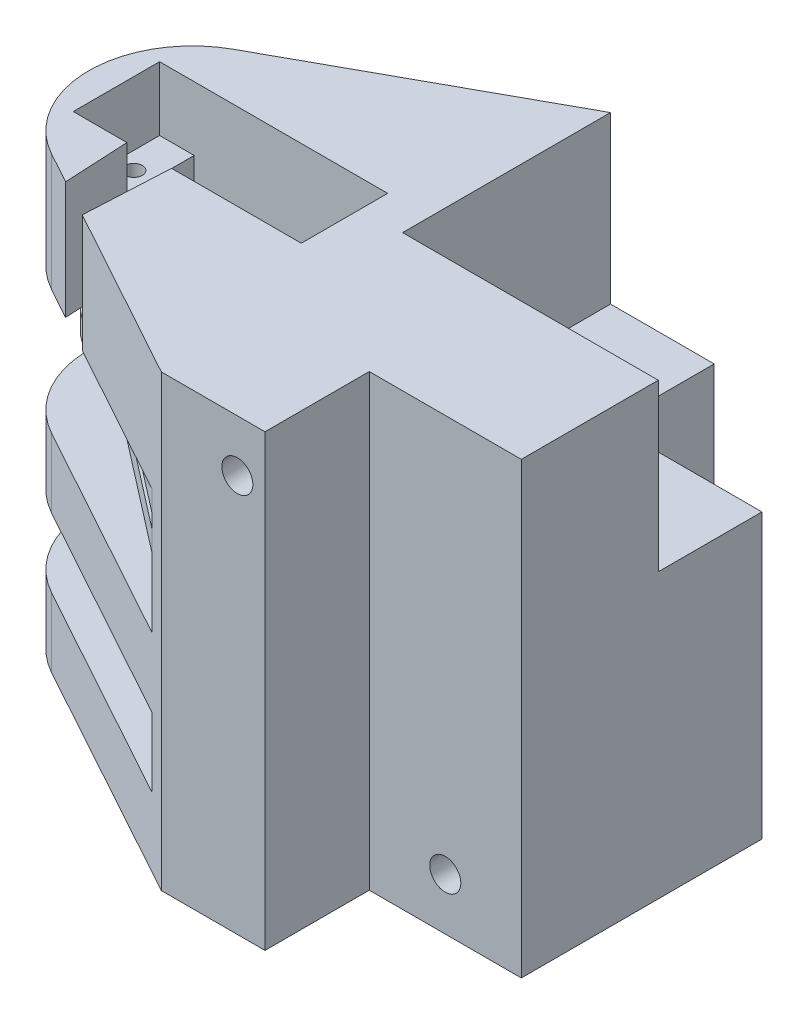
SolidWorks part; units mm, degrees
material "Copper"
ref_plane "Front Plane" through (0, 0, 0) normal (0, 0, 1) x (1, 0, 0)
ref_plane "Top Plane" through (0, 0, 0) normal (0, 1, 0) x (1, 0, 0)
ref_plane "Right Plane" through (0, 0, 0) normal (1, 0, 0) x (0, 0, -1)
sketch "Sketch1" plane through (0, 0, 0) normal (0, 0, 1) x (1, 0, 0)
  line L1 (0, 0) -> (80, 0)
  line L2 (0, 0) -> (0, 65)
  line L3 (0, 65) -> (80, 65)
  line L4 (80, 0) -> (80, 65)
  dimension "D1" = 65
  dimension "D2" = 80
extrude "Boss-Extrude1" add sketch "Sketch1" along normal blind 65
sketch "Sketch3" plane through (0, 0, 0) normal (0, -1, 0) x (1, 0, 0)
  line L0 (80, 32.5) -> (0, 32.5) construction
  line L1 (80, 65) -> (80, 0) construction
  line L2 (0, 65) -> (0, 0) construction
  line L3 (58, 49.91) -> (58, 32.5) construction
  line L4 (80, 65) -> (58, 65)
  line L5 (80, 65) -> (80, 49.91)
  line L6 (80, 49.91) -> (58, 49.91)
  line L7 (58, 65) -> (58, 49.91)
  line L8 (80, 0) -> (58, 0)
  line L9 (80, 0) -> (80, 15.09)
  line L10 (80, 15.09) -> (58, 15.09)
  line L11 (58, 0) -> (58, 15.09)
  line L12 (58, 32.5) -> (58, 15.09) construction
  dimension "D1" = 22
  dimension "D2" = 17.41
extrude "Cut-Extrude1" cut sketch "Sketch3" against normal blind 65.72
sketch "Sketch4" plane through (0, 0, 49.91) normal (0, 0, 1) x (1, 0, 0)
  line L0 (69, 0) -> (69, 65) construction
  line L1 (58, 0) -> (80, 0) construction
  line L2 (69, 7.5) -> (69, 0) construction
  line L3 (58, 65) -> (80, 65) construction
  line L4 (69, 65) -> (69, 57.5) construction
  line L5 (69, 57.5) -> (54, 57.5) construction
  circle A0 centre (69, 7.5) radius 2.2451
  circle A1 centre (69, 57.5) radius 2.2451
  circle A2 centre (54, 57.5) radius 2.245
  dimension "D1" = 4.4901
  dimension "D3" = 7.5
  dimension "D4" = 4.4901
  dimension "D5" = 4.49
  dimension "D2" = 7.5
  dimension "D6" = 15
extrude "Cut-Extrude2" cut sketch "Sketch4" against normal blind 55.72 and the other way blind 20 contours A2 | A0 region at (54, 57.5, 49.91)
sketch "Sketch5" plane through (0, 0, 0) normal (-1, 0, 0) x (0, 0, 1)
  line L0 (65, 65) -> (65, 0) construction
  line L1 (0, 0) -> (65, 0)
  line L2 (0, 0) -> (0, 10)
  line L3 (0, 10) -> (65, 10)
  line L4 (65, 0) -> (65, 10)
  line L6 (0, 10) -> (65, 10)
  line L7 (0, 10) -> (0, 20)
  line L8 (0, 20) -> (65, 20)
  line L9 (65, 10) -> (65, 20)
  line L10 (0, 20) -> (65, 20)
  line L11 (0, 20) -> (0, 30)
  line L12 (0, 30) -> (65, 30)
  line L13 (65, 20) -> (65, 30)
  line L14 (0, 30) -> (65, 30)
  line L15 (0, 30) -> (0, 40)
  line L16 (0, 40) -> (65, 40)
  line L17 (65, 30) -> (65, 40)
  line L18 (0, 40) -> (65, 40)
  line L19 (0, 40) -> (0, 43)
  line L20 (0, 43) -> (65, 43)
  line L21 (65, 40) -> (65, 43)
  line L22 (0, 43) -> (65, 43)
  line L23 (0, 43) -> (0, 45)
  line L24 (0, 45) -> (65, 45)
  line L25 (65, 43) -> (65, 45)
  line M3 (0, 65) -> (0, 0)
  line M5 (65, 0) -> (65, 65)
  dimension "D1" = 10
  dimension "D2" = 3
  dimension "D3" = 2
extrude "Cut-Extrude3" cut sketch "Sketch5" against normal blind 40 contours L16 L12 M3 M5 | L8 L3 M3 M5 | L23 L24 L25 L22 region at (0, 15, 32.5) region at (0, 35, 32.5)
sketch "Sketch6" plane through (0, 0, 0) normal (0, -1, 0) x (1, 0, 0)
  line L0 (0, 32.5) -> (48.8784, 32.5) construction
  line L1 (0, 65) -> (0, 0) construction
  line L2 (58, 0) -> (43, 0)
  line L3 (0, 0) -> (58, 0) construction
  line L4 (43, 0) -> (7.7767, 19.3538)
  line L5 (7.7767, 45.6462) -> (43, 65)
  line L6 (0, 65) -> (58, 65) construction
  line L7 (43, 0) -> (43, 65) construction
  line L8 (58, 15.09) -> (58, 0) construction
  line L9 (43, 14.0738) -> (58, 14.0738) construction
  line L10 (43, 0) -> (0, 0)
  line L11 (0, 0) -> (0, 32.5)
  line L12 (0, 32.5) -> (0, 65)
  line L13 (0, 65) -> (43, 65)
  circle A0 centre (15, 32.5) radius 15
  line M6 (58, 65) -> (0, 65)
  line M7 (0, 65) -> (0, 0)
  line M8 (0, 0) -> (58, 0)
  dimension "D1" = 15
  dimension "D2" = 30
extrude "Cut-Extrude4" cut sketch "Sketch6" against normal blind 65 contours A0 L4 M7 M8 | A0 L5 M6 M7 region at (14.0187, 0, 8.2899) region at (14.0187, 0, 56.7101)
sketch "Sketch10" plane through (0, 0, 0) normal (0, -1, 0) x (1, 0, 0)
  line L0 (0, 32.5) -> (15, 32.5) construction
  arc A0 (7.7767, 45.6462) -> (7.7767, 19.3538) centre (15, 32.5) ccw construction
  circle A1 centre (15, 32.5) radius 1
  dimension "D1" = 15
  dimension "D2" = 2
extrude "Cut-Extrude6" cut sketch "Sketch10" against normal blind 42
sketch "Sketch12" plane through (0, 65, 0) normal (0, 1, 0) x (1, 0, 0)
  line L0 (0, -32.5) -> (43.2089, -32.5) construction
  line L2 (15, -32.5) -> (0, -32.5) construction
  line L3 (20.2526, -29.6) -> (21.4526, -29.6)
  line L4 (21.4526, -35.4) -> (20.2526, -35.4)
  circle A0 centre (15, -32.5) radius 6
  circle A1 centre (21.4526, -32.5) radius 2.9
  arc A2 (7.7767, -19.3538) -> (7.7767, -45.6462) centre (15, -32.5) ccw construction
  dimension "D1" = 12
  dimension "D3" = 5.8
  dimension "D2" = 15
  dimension "D4" = 1.2
extrude "Cut-Extrude7" cut sketch "Sketch12" against normal blind 20 contours A1 A0 | A1 A0 | A0 A1 | A1 L3 A0 | A1 A0 L4 | A0 region at (14.5616, 65, 32.5) region at (20.5934, 65, 29.6641) region at (22.3237, 65, 32.5) region at (20.5934, 65, 35.3359) region at (19.8631, 65, 32.5)
sketch "Sketch14" plane through (0, 65, 0) normal (0, 1, 0) x (1, 0, 0)
  line L0 (0, -32.5) -> (49.7472, -32.5) construction
  line L2 (32, -32.5) -> (49.7472, -32.5) construction
  line L3 (9, -26.25) -> (32, -26.25)
  line L4 (9, -26.25) -> (9, -38.75)
  line L5 (9, -38.75) -> (32, -38.75)
  line L6 (32, -26.25) -> (32, -38.75)
  line L7 (15, -26.5) -> (15, -38.5) construction
  line L8 (32, -32.5) -> (24.3526, -32.5) construction
  line L9 (15, -26.5) -> (15, -26.25) construction
  arc A0 (20.2526, -29.6) -> (20.2526, -35.4) centre (15, -32.5) ccw construction
  arc A1 (21.4526, -35.4) -> (21.4526, -29.6) centre (21.4526, -32.5) ccw construction
  arc A2 (7.7767, -19.3538) -> (7.7767, -45.6462) centre (15, -32.5) ccw construction
  dimension "D1" = 23
  dimension "D2" = 12.5
extrude "Cut-Extrude9" cut sketch "Sketch14" against normal blind 13.75
sketch "Sketch16" plane through (0, 65, 0) normal (0, 1, 0) x (1, 0, 0)
  line L0 (32, -26.25) -> (9, -26.25) construction
  line L1 (9, -38.75) -> (4, -38.75)
  line L2 (9, -38.75) -> (9, -26.25)
  line L3 (9, -26.25) -> (4, -26.25)
  line L4 (4, -38.75) -> (4, -26.25)
  line L5 (32, -26.25) -> (37, -26.25)
  line L6 (32, -26.25) -> (32, -38.75)
  line L7 (32, -38.75) -> (37, -38.75)
  line L8 (37, -26.25) -> (37, -38.75)
  line L9 (4, -32.5) -> (9, -32.5) construction
  line L10 (32, -32.5) -> (37, -32.5) construction
  circle A2 centre (6.5, -32.5) radius 1.25
  circle A3 centre (34.5, -32.5) radius 1.25
  line M8 (9, -38.75) -> (9, -26.25)
  line M10 (32, -26.25) -> (32, -38.75)
  dimension "D2" = 2.5
  dimension "D1" = 5
extrude "Cut-Extrude10" cut sketch "Sketch16" against normal blind 9.25 contours A2 | L4 L1 L3 A2 M8 | L8 L5 L7 A3 M10 | A3 region at (6.5, 65, 38.6154) region at (34.5, 65, 26.3846) region at (6.5, 65, 32.5) region at (34.5, 65, 32.5)
extrude "Cut-Extrude11" cut sketch "Sketch16<4>" against normal blind 12.5 contours A2 | A3 region at (6.5, 65, 32.5) region at (34.5, 65, 32.5)
sketch "Sketch16<4>" plane through (0, 65, 0) normal (0, 1, 0) x (1, 0, 0) same geometry as "Sketch16"
sketch "Sketch18" plane through (0, 65, 0) normal (0, 1, 0) x (1, 0, 0)
  line L0 (15, -32.5) -> (0, -32.5) construction
  line L1 (11.45, -29) -> (18.55, -29)
  line L2 (11.45, -29) -> (11.45, -52.0042)
  line L3 (11.45, -52.0042) -> (18.55, -52.0042)
  line L4 (18.55, -29) -> (18.55, -52.0042)
  line L5 (15, -29) -> (15, -32.5) construction
  line L6 (11.45, -32.5) -> (12.45, -52.0042)
  line L7 (18.55, -32.5) -> (17.55, -52.0042)
  line L8 (12.45, -52.0042) -> (11.45, -52.0042) construction
  line L9 (17.55, -52.0042) -> (18.55, -52.0042) construction
  arc A0 (7.7767, -19.3538) -> (7.7767, -45.6462) centre (15, -32.5) ccw construction
  circle A2 centre (15, -32.5) radius 3.55
  line M9 (37, -38.75) -> (4, -38.75)
  line M11 (7.7767, -45.6462) -> (43, -65)
  dimension "D1" = 3.5
  dimension "D2" = 7.1
  dimension "D3" = 1
extrude "Cut-Extrude12" cut sketch "Sketch18" against normal blind 21.5 contours A2 L6 L7 M9 | L7 A2 L1 L6 | L1 A2 | L7 L6 M9 M11 region at (15, 65, 28.98) region at (15, 65, 32.5035) region at (15, 65, 36.9512) region at (15.1094, 65, 44.0321)
sketch "Sketch19" plane through (0, 40, 0) normal (0, -1, 0) x (1, 0, 0)
  line L0 (40, 63.3516) -> (15, 44)
  line L1 (40, 1.6484) -> (15, 21)
  circle A2 centre (15, 32.5) radius 11.5
  line M2 (40, 63.3516) -> (7.7767, 45.6462)
  arc M3 (7.7767, 45.6462) -> (7.7767, 19.3538) centre (15, 32.5) ccw
  line M4 (7.7767, 19.3538) -> (40, 1.6484)
  dimension "D1" = 23
extrude "Cut-Extrude13" cut sketch "Sketch19" against normal blind 8 contours A2 L0 L1 M2 M3 M4 region at (27.0499, 40, 54.2573)
sketch "Sketch20" plane through (0, 30, 0) normal (0, 1, 0) x (1, 0, 0)
  circle A0 centre (15, -32.5) radius 2
  dimension "D1" = 4
extrude "Boss-Extrude2" add sketch "Sketch20" along normal blind 0.5
sketch "Sketch21" plane through (0, 10, 0) normal (0, 1, 0) x (1, 0, 0)
  circle A0 centre (15, -32.5) radius 2
extrude "Boss-Extrude3" add sketch "Sketch21" along normal blind 0.5
sketch "Sketch22" plane through (0, 0, 0) normal (0, -1, 0) x (1, 0, 0)
  circle A0 centre (15, 32.5) radius 1
extrude "Cut-Extrude14" cut sketch "Sketch22" against normal blind 30.5
sketch "Sketch23" plane through (0, 65, 0) normal (0, 1, 0) x (1, 0, 0)
  line L0 (80, -49.91) -> (80, -15.09) construction
  line L1 (43, 0) -> (80, 0)
  line L2 (43, 0) -> (43, -30.09)
  line L3 (43, -30.09) -> (80, -30.09)
  line L4 (80, 0) -> (80, -30.09)
  line L5 (58, 0) -> (43, 0) construction
  line L6 (80, -15.09) -> (58, -15.09) construction
  dimension "D1" = 37
  dimension "D2" = 15
extrude "Cut-Extrude15" cut sketch "Sketch23" against normal blind 24
